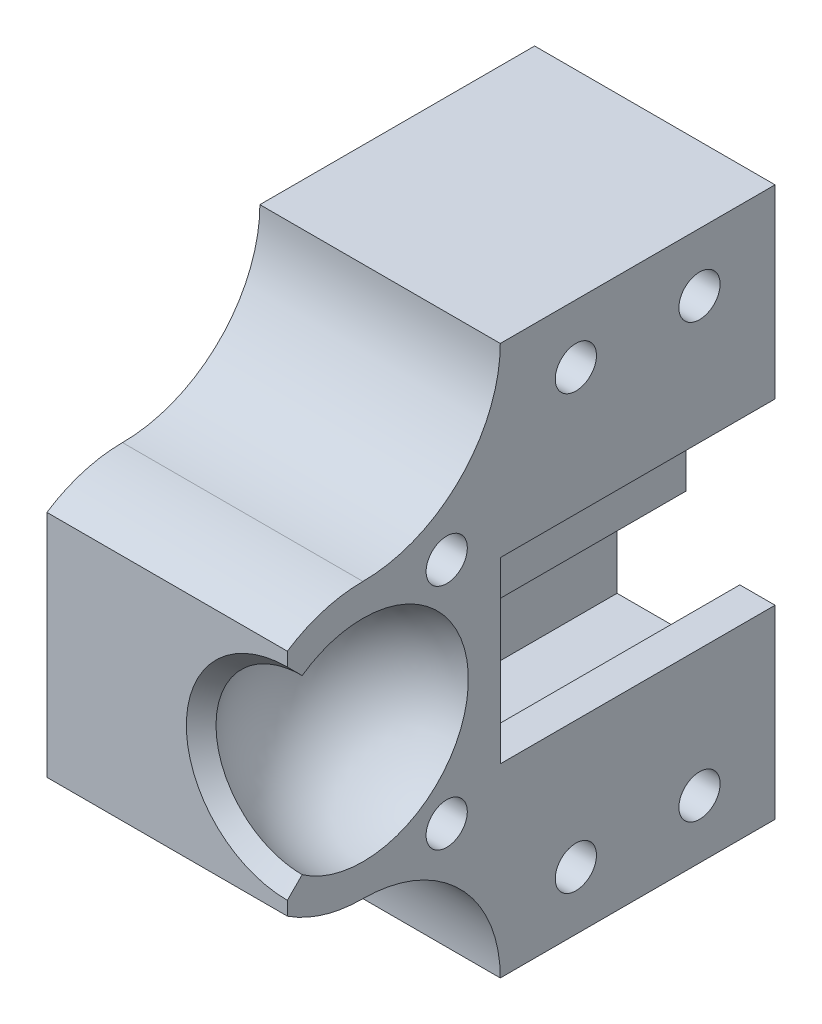
SolidWorks part; units mm, degrees
ref_plane "Front Plane" through (0, 0, 0) normal (0, 0, 1) x (1, 0, 0)
ref_plane "Top Plane" through (0, 0, 0) normal (0, 1, 0) x (1, 0, 0)
ref_plane "Right Plane" through (0, 0, 0) normal (1, 0, 0) x (0, 0, -1)
sketch "Sketch1" plane through (0, 0, 0) normal (0, 0, 1) x (1, 0, 0)
  line L0 (-11, -4.5) -> (-11, 9)
  line L2 (-11, 9) -> (-28.5, 9)
  line L3 (-28.5, 9) -> (-28.5, -11)
  line L13 (-22.5, 0.5) -> (-13.5, 0.5)
  line L14 (-13.5, 0.5) -> (-13.5, -1.8)
  line L19 (-11, -4.5) -> (-11, -17.5) construction
  line L20 (-16.5, -11) -> (-11, -11) construction
  line L21 (-16.5, -14) -> (-16.5, -8) construction
  line L22 (-28.5, -11) -> (-17.5, -11)
  line L23 (-16.5, -11) -> (-17.5, -11) construction
  line L24 (-22.5, -8.5) -> (-20.2, -8.5)
  line L25 (-20.2, -8.5) -> (-18.8591, -7.1591)
  line L26 (-18.8591, -7.1591) -> (-17.5, -8.4332)
  line L27 (-17.5, -8.4332) -> (-17.5, -11)
  line L29 (-22.5, 0.5) -> (-22.5, -8.5)
  line L30 (-22, -8) -> (-22, 0) construction
  line L31 (-13.5, -1.8) -> (-14.8409, -3.1409)
  line L32 (-14.8409, -3.1409) -> (-13.5668, -4.5)
  line L33 (-13.5668, -4.5) -> (-11, -4.5)
  line L34 (-16.5, -8) -> (-19.7, -5) construction
  line L35 (-17, -2.3) -> (-14, -5.5) construction
  line L36 (-14, -5.5) -> (-8, -5.5) construction
  line L37 (-20.7, -8) -> (-22, -8) construction
  line L38 (-14, 0) -> (-14, -1.3) construction
  line L39 (-20.7, -8) -> (-20.2, -8.5) construction
  line L40 (-14, -1.3) -> (-13.5, -1.8) construction
  line L41 (-22, 0) -> (-14, 0) construction
  point P41 (-22, -4)
  point P45 (-11, -5.5)
  dimension "D1" = 1
  dimension "D2" = 1
  dimension "D3" = 1
  dimension "D4" = 1
  dimension "D5" = 0.5
  dimension "D6" = 0.5
  dimension "D7" = 0.5
  dimension "D8" = 0.5
  dimension "D9" = 6
  dimension "D10" = 8.5
extrude "Boss-Extrude1" add sketch "Sketch1" against normal blind 20
mirror "Mirror1" about plane through (-28.5, -11, -20) normal (0, -1, 0) of bodies 101
sketch "Sketch2" plane through (0, 0, 0) normal (0, 0, 1) x (1, 0, 0)
  line L1 (-11, 9) -> (-28.5, 9)
  line L2 (-11, 9) -> (-11, -31)
  line L3 (-11, -31) -> (-28.5, -31)
  line L4 (-28.5, 9) -> (-28.5, -31)
extrude "Boss-Extrude2" add sketch "Sketch2" along normal blind 20
sketch "Sketch3" plane through (-11, 0, 0) normal (1, 0, 0) x (0, 0, -1)
  line L0 (20, 9) -> (-20, 9) construction
  line L1 (20, -31) -> (-20, -31) construction
  line L2 (-20, -31) -> (-20, 9) construction
  line L3 (0, 9) -> (0, -31) construction
  line L4 (-10, -1) -> (-10, -21) construction
  line L5 (-15.5, -2.6484) -> (-15.5, -19.3516)
  line L6 (0, 9) -> (-20, 9)
  line L7 (-20, 9) -> (-20, -31)
  line L8 (-20, -31) -> (0, -31)
  arc A0 (-10, -1) -> (-15.5, -2.6484) centre (-10, -11) ccw
  arc A1 (0, 9) -> (-10, -1) centre (-10, 9) cw
  arc A2 (-10, -21) -> (0, -31) centre (-10, -31) cw
  arc A3 (-15.5, -19.3516) -> (-10, -21) centre (-10, -11) ccw
  arc A4 (-15.5, -2.6484) -> (-15.5, -19.3516) centre (-10, -11) ccw construction
  dimension "D1" = 10
  dimension "D2" = 4.5
extrude "Cut-Extrude1" cut sketch "Sketch3" against normal through all
sketch "Sketch4" plane through (-11, 0, 0) normal (1, 0, 0) x (0, 0, -1)
  line L0 (-10, -1) -> (-10, -21) construction
  circle A0 centre (-10, -11) radius 7.675
  dimension "D1" = 15.35
revolve "Cut-Revolve2" cut sketch "Sketch4" angle 360 about L0 region at (-11, -11, 6.7426)
chamfer "Chamfer1" distance 2 angle 45 1 edges at (-16.3531, -11, 15.5) first distance on face at (-17.7255, -11, 15.5)
sketch "Sketch5" plane through (-11, 0, 0) normal (1, 0, 0) x (0, 0, -1)
  line L0 (14.5, 4.75) -> (5.5, 4.75) construction
  line L1 (20, 4.75) -> (14.5, 4.75) construction
  line L2 (20, -4.5) -> (20, 9) construction
  line L4 (20, 0.5) -> (20, 9) construction
  line L5 (0, 9) -> (0, 4.75) construction
  line L6 (5.5, 4.75) -> (0, 4.75) construction
  line L7 (-3.9005, -2.6873) -> (-3.0904, -7.6589) construction
  line L8 (-3.0904, -7.6589) -> (-8.611, -0.9031) construction
  line L9 (0, 0.5) -> (-3.9005, -2.6873) construction
  line L10 (-3.9005, -2.6873) -> (-8.611, -0.9031) construction
  line L11 (-8.611, -0.9031) -> (0, 0.5) construction
  line L12 (0, 0.5) -> (-3.0904, -7.6589) construction
  circle A0 centre (5.5, 4.75) radius 1.5
  circle A1 centre (14.5, 4.75) radius 1.5
  circle A2 centre (-3.9005, -2.6873) radius 1.5
  arc A3 (-14.4208, -17.2739) -> (-14.4208, -4.7261) centre (-10, -11) ccw construction
  arc A4 (-10, -1) -> (0, 9) centre (-10, 9) ccw construction
  point P5 (20, 0.5)
  dimension "D1" = 9
  dimension "D2" = 3
extrude "Cut-Extrude2" cut sketch "Sketch5" against normal through all
ref_plane "Plane1" through (0, -11, 0) normal (0, 1, 0) x (1, 0, 0)
chamfer "Chamfer2" [suppressed] distance 2 angle 45
sketch "Sketch6" plane through (-28.5, 0, 0) normal (-1, 0, 0) x (0, 0, 1)
  line L0 (-16.2321, 7.75) -> (-12.7679, 7.75)
  line L1 (-12.7679, 7.75) -> (-11.0359, 4.75)
  line L2 (-11.0359, 4.75) -> (-12.7679, 1.75)
  line L3 (-12.7679, 1.75) -> (-16.2321, 1.75)
  line L4 (-16.2321, 1.75) -> (-17.9641, 4.75)
  line L5 (-17.9641, 4.75) -> (-16.2321, 7.75)
  circle A0 centre (-14.5, 4.75) radius 3.4641 construction
  point P5 (-5.5, 4.75)
  dimension "D1" = 6
extrude "Cut-Extrude3" cut sketch "Sketch6" against normal blind 3
pattern_sketch "Sketch-Pattern1" of "Cut-Extrude3" driven by "Sketch6"
sketch "Sketch10" plane through (-28.5, 0, 0) normal (-1, 0, 0) x (0, 0, 1)
  line L0 (3.9005, 0.7768) -> (6.9005, -0.9553)
  line L1 (6.9005, -0.9553) -> (6.9005, -4.4194)
  line L2 (6.9005, -4.4194) -> (3.9005, -6.1514)
  line L3 (3.9005, -6.1514) -> (0.9005, -4.4194)
  line L4 (0.9005, -4.4194) -> (0.9005, -0.9553)
  line L5 (0.9005, -0.9553) -> (3.9005, 0.7768)
  circle A0 centre (3.9005, -2.6873) radius 3.4641 construction
  dimension "D1" = 6
extrude "Cut-Extrude6" cut sketch "Sketch10" against normal blind 3
mirror "Mirror2" [suppressed] about plane through (0, -11, 0) normal (0, 1, 0)
mirror "Mirror3" about plane through (0, -11, 0) normal (0, 1, 0) of "Cut-Extrude6", "Cut-Extrude2", "Cut-Extrude3", "Sketch-Pattern1"
sketch "Sketch7" [suppressed] plane through (0, -11, 0) normal (0, 1, 0) x (1, 0, 0)
  line L0 (-28.5, -14) -> (-21, -14)
  line L1 (-21, -14) -> (-11, -24)
  line L2 (-11, -24) -> (-28.5, -24)
  line L3 (-28.5, -24) -> (-28.5, -14)
  line L4 (-28.5, 13.201) -> (-28.5, 6.799) construction
  line L5 (-28.5, -15.5) -> (-11, -15.5) construction
  dimension "D1" = 7.5
  dimension "D2" = 1.5
  dimension "D3" = 135
  dimension "D4" = 10
extrude "Cut-Extrude4" [suppressed] cut sketch "Sketch7" against normal mid plane 23
fillet "Fillet1" [suppressed] radius 3
sketch "Sketch9" [suppressed] plane through (-17.5, 0, 17.5) normal (-0.7071, 0, 0.7071) x (0.7071, 0, 0.7071)
  line L0 (-2.8284, -11) -> (-1.3284, -11) construction
  line L1 (-2.8284, -4.8694) -> (-2.8284, -17.1306) construction
  line L2 (-1.3284, -16.5) -> (-1.3284, -5.5) construction
  ellipse E0 centre (-1.3284, -11) end of major axis (-1.3284, -5.5) minor radius 3.75
  dimension "D1" = 7.5
  dimension "D2" = 11
  dimension "D3" = 1.5
extrude "Cut-Extrude5" [suppressed] cut sketch "Sketch9" against normal through all
